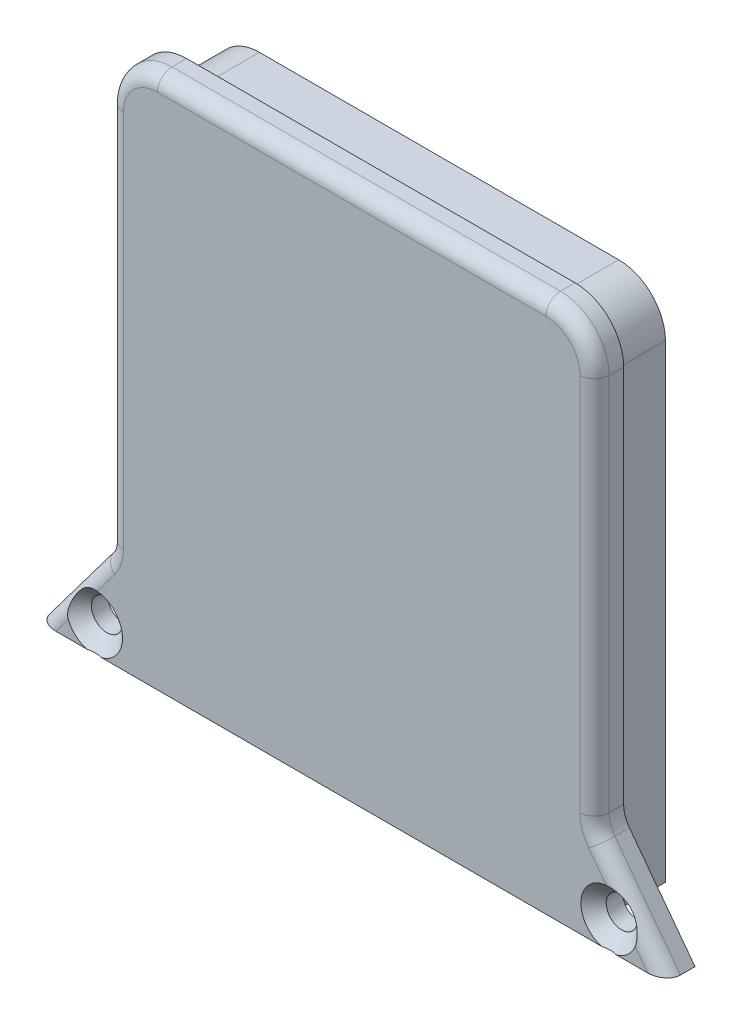
SolidWorks part; units mm, degrees
ref_plane "Front Plane" through (0, 0, 0) normal (0, 0, 1) x (1, 0, 0)
ref_plane "Top Plane" through (0, 0, 0) normal (0, 1, 0) x (1, 0, 0)
ref_plane "Right Plane" through (0, 0, 0) normal (1, 0, 0) x (0, 0, -1)
sketch "Sketch1" plane through (0, 0, 0) normal (0, 0, 1) x (1, 0, 0)
  line L37 (-29.5, 2.2) -> (29.5, 2.2)
  line L38 (-23.3, 50.5) -> (-23.3, 2)
  line L39 (23.3, 2) -> (23.3, 50.5)
  line L40 (18.5, 55.3) -> (-18.5, 55.3)
  line L41 (-23.3, 50.5) -> (-23.3, 2.2)
  line L42 (23.3, 2.2) -> (23.3, 50.5)
  line L43 (18.5, 55.3) -> (-18.5, 55.3)
  line L44 (-23.3, 2.2) -> (23.3, 2.2)
  arc A35 (23.3, 50.5) -> (18.5, 55.3) centre (18.5, 50.5) ccw
  arc A36 (-18.5, 55.3) -> (-23.3, 50.5) centre (-18.5, 50.5) ccw
  arc A37 (23.3, 50.5) -> (18.5, 55.3) centre (18.5, 50.5) ccw
  arc A38 (-18.5, 55.3) -> (-23.3, 50.5) centre (-18.5, 50.5) ccw
  dimension "D1" = 0.2
  dimension "D2" = 0.2
extrude "Boss-Extrude1" add sketch "Sketch1" against normal blind 6
sketch "Sketch2" plane through (0, 0, 0) normal (0, 0, 1) x (1, 0, 0)
  line L0 (-25.6, 11.2) -> (-32.5, 2) construction
  line L1 (-25, 52) -> (-25, 13) construction
  line L2 (32.5, 2) -> (25.6, 11.2) construction
  line L3 (25, 13) -> (25, 52) construction
  line L4 (20, 57) -> (-20, 57) construction
  line L5 (-25.6, 11.2) -> (-32.35, 2.2)
  line L6 (-25, 52) -> (-25, 13)
  line L7 (32.35, 2.2) -> (25.6, 11.2)
  line L8 (25, 13) -> (25, 52)
  line L9 (20, 57) -> (-20, 57)
  line L10 (-23.3, 2.2) -> (-32.35, 2.2)
  line L11 (23.3, 2.2) -> (32.35, 2.2)
  line L12 (-23.3, 2.2) -> (23.3, 2.2)
  arc A0 (-25.6, 11.2) -> (-25, 13) centre (-28, 13) ccw construction
  arc A1 (25, 13) -> (25.6, 11.2) centre (28, 13) ccw construction
  arc A2 (25, 52) -> (20, 57) centre (20, 52) ccw construction
  arc A3 (-20, 57) -> (-25, 52) centre (-20, 52) ccw construction
  arc A4 (-25.6, 11.2) -> (-25, 13) centre (-28, 13) ccw
  arc A5 (25, 13) -> (25.6, 11.2) centre (28, 13) ccw
  arc A6 (25, 52) -> (20, 57) centre (20, 52) ccw
  arc A7 (-20, 57) -> (-25, 52) centre (-20, 52) ccw
extrude "Boss-Extrude2" add sketch "Sketch2" along normal blind 3
sketch "Sketch3" plane through (0, 0, 3) normal (0, 0, 1) x (1, 0, 0)
  circle A0 centre (-26.5, 5) radius 1.6
  circle A1 centre (26.5, 5) radius 1.6
  dimension "D1" = 3.2
  dimension "D2" = 3.2
extrude "Cut-Extrude1" cut sketch "Sketch3" against normal through all
chamfer "Chamfer1" distance 1.3 angle 45 2 edges at (28.1, 5, 3) (-24.9, 5, 3)
fillet "Fillet1" radius 1.5 9 edges at (28.975, 6.7, 3) (25.154, 12.0513, 3) (25, 32.5, 3) (23.5355, 55.5355, 3) (0, 57, 3) (-23.5355, 55.5355, 3) (-28.975, 6.7, 3) (-25.154, 12.0513, 3) (-25, 32.5, 3)
